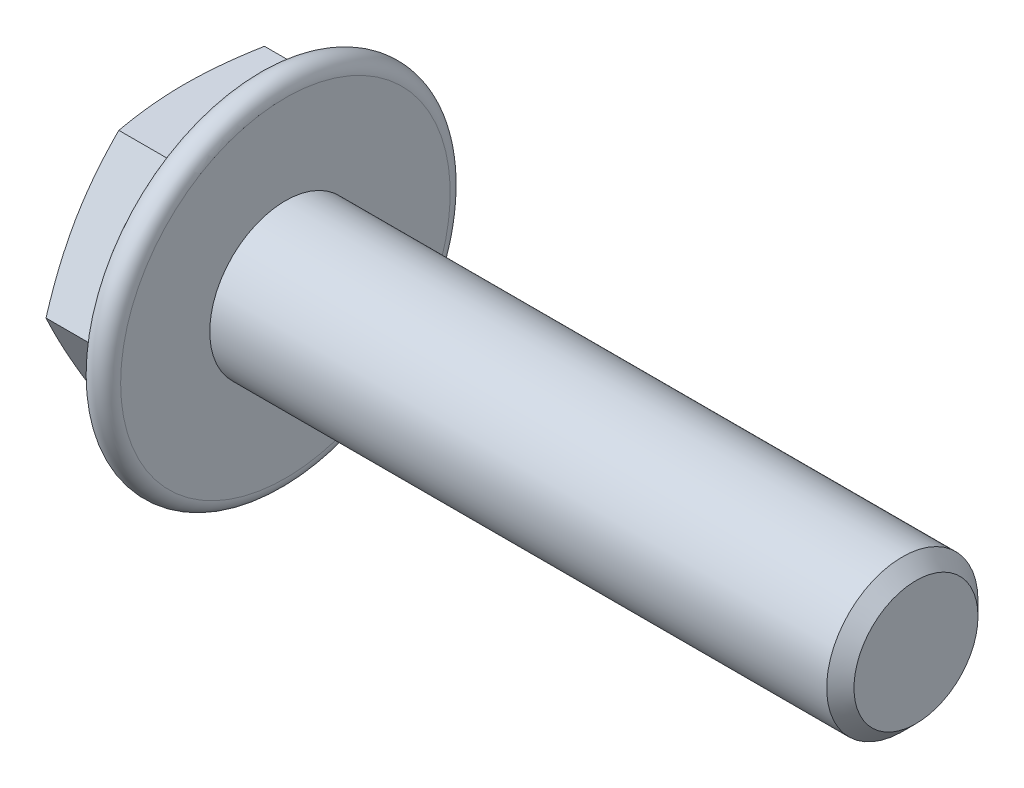
SolidWorks part; units mm, degrees
ref_plane "Front" through (0, 0, 0) normal (0, 0, 1) x (1, 0, 0)
ref_plane "Top" through (0, 0, 0) normal (0, 1, 0) x (1, 0, 0)
ref_plane "Right" through (0, 0, 0) normal (1, 0, 0) x (0, 0, -1)
other "Configuration Table"
sketch "Sketch1" plane through (0, 0, 0) normal (1, 0, 0) x (0, 0, -1)
  line L1 (5.7735, 0) -> (2.8868, 5)
  line L2 (2.8868, 5) -> (-2.8868, 5)
  line L3 (-2.8868, 5) -> (-5.7735, 0)
  line L4 (-5.7735, 0) -> (-2.8868, -5)
  line L5 (-2.8868, -5) -> (2.8868, -5)
  line L6 (2.8868, -5) -> (5.7735, 0)
  circle A0 centre (0, 0) radius 5 construction
extrude "BaseHead" add sketch "Sketch1" along normal blind 4
ref_plane "Plane1" through (12, 0, 0) normal (1, 0, 0) x (0, 0, -1)
sketch "Sketch2" plane through (4, 0, 0) normal (1, 0, 0) x (0, 0, -1)
  circle A0 centre (0, 0) radius 3
extrude "BaseBody" add sketch "Sketch2" along normal blind 25
cosmetic thread "ThreadCosmetic1" [suppressed] parameters "b"=17, "D2"=4.917
sketch "Sketch3" plane through (-0.4952, 0, 6.2687) normal (0, 1, 0) x (0, 0, -1)
  line L0 (12.0422, -0.4952) -> (12.0422, -0.7767)
  line L2 (12.0422, -0.7767) -> (11.2687, -0.4952)
  line L4 (11.2687, -0.4952) -> (12.0422, -0.4952)
  line L5 (6.2687, 4.1693) -> (6.2687, -11.9236) construction
  dimension "D1" = 20
revolve "HeadChamfer" cut sketch "Sketch3" angle 360 about L5
sketch "Sketch5" plane through (-0.1752, 0, 7.2752) normal (0, 1, 0) x (0, 0, -1)
  line L0 (7.2752, -4.1752) -> (7.2752, -7.1738) construction
  line L2 (7.2752, -4.1752) -> (13.8081, -4.1752)
  line L3 (14.002, -3.0752) -> (7.2752, -0.6268)
  line L4 (7.2752, -0.6268) -> (7.2752, -4.1752)
  line L7 (7.2752, 4.4893) -> (7.2752, -11.6035) construction
  arc A0 (13.8081, -4.1752) -> (14.002, -3.0752) centre (13.8081, -3.6081) ccw
  dimension "D3" = 20
  dimension "c" = 1.1
  dimension "dc" = 14.2
revolve "Flange" add sketch "Sketch5" angle 360 about L0
fillet "HeadFillet" [suppressed] radius 0.3
fillet "FlangeHexFillet" radius 0.4 6 edges
chamfer "Chamfer1" distance 0.5415 angle 45 1 edges at (29, 0, -3)
sketch "Sketch6" plane through (0, 0, 0) normal (0, 0, 1) x (1, 0, 0)
  line L0 (27.917, 3.5415) -> (28.4585, 3.5415)
  line L1 (28.4585, 3.5415) -> (28.4585, 3)
  line L2 (28.4585, 3) -> (28.1877, 2.531)
  line L3 (28.1877, 2.531) -> (27.917, 3)
  line L4 (27.917, 3) -> (27.917, 3.5415)
  line L5 (28.4585, 3) -> (4, 3) construction
revolve "Cut-Revolve10" [suppressed] cut sketch "Sketch6" angle 360
pattern_linear "LPattern10" [suppressed] count 26 of bodies 106
equation "\"D1@Chamfer1\" = (  \"d@Sketch2\" - \"D2@ThreadCosmetic1\" )  / 2"
equation "\"b@ThreadCosmetic1\" = \"l@BaseBody\" - \"lg@Plane1\""
equation "\"da@Sketch3\" = \"s@Sketch1\""
equation "\"D1@Sketch6\" =  ( \"d@Sketch2\" - \"D2@ThreadCosmetic1\" )  / 2"
equation "\"pitch@LPattern10\" = 1.2 * \"D1@Sketch6\""
equation "\"D1@LPattern10\" = \"b@ThreadCosmetic1\" / \"pitch@LPattern10\""
